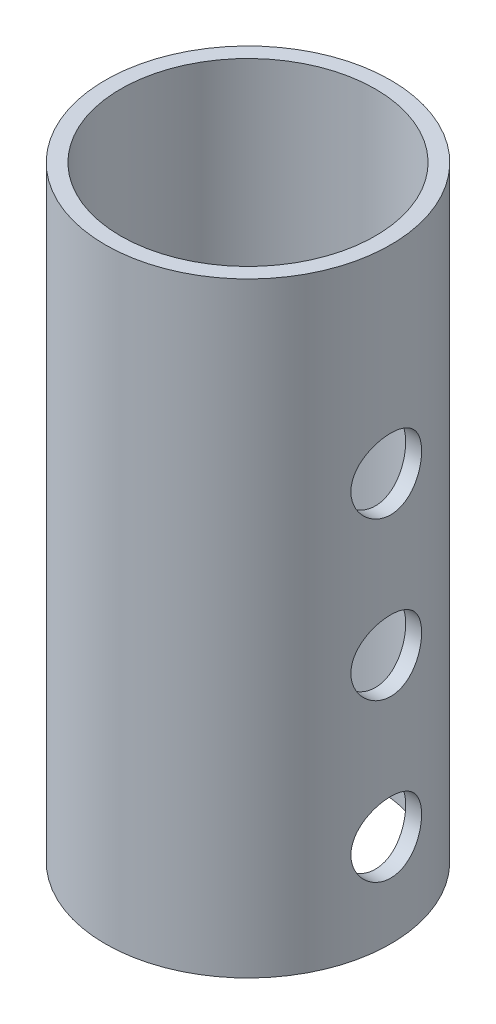
SolidWorks part; units mm, degrees
material "PTFE (general)"
ref_plane "Front Plane" through (0, 0, 0) normal (0, 0, 1) x (1, 0, 0)
ref_plane "Top Plane" through (0, 0, 0) normal (0, 1, 0) x (1, 0, 0)
ref_plane "Right Plane" through (0, 0, 0) normal (1, 0, 0) x (0, 0, -1)
sketch "Sketch1" plane through (0, 0, 0) normal (0, 1, 0) x (1, 0, 0)
  circle A0 centre (0, 0) radius 46.53
  circle A1 centre (0, 0) radius 41.53
  dimension "D1" = 5
  dimension "D2" = 83.06
extrude "Boss-Extrude1" add sketch "Sketch1" along normal blind 197.41
sketch "Sketch2" plane through (0, 0, 0) normal (1, 0, 0) x (0, 0, -1)
  line L0 (41.53, 197.41) -> (-41.53, 197.41) construction
  circle A0 centre (0, 132.71) radius 11.53
  circle A1 centre (0, 81.41) radius 11.53
  circle A2 centre (0, 30.11) radius 11.53
  dimension "D2" = 23.06
  dimension "D3" = 23.06
  dimension "D4" = 23.06
  dimension "D1" = 64.7
  dimension "D5" = 51.3
  dimension "D6" = 51.3
extrude "Cut-Extrude1" cut sketch "Sketch2" along normal through all
sketch "Sketch4" plane through (0, 0, 0) normal (1, 0, 0) x (0, 0, -1)
  circle A0 centre (0, 106.91) radius 7.5
  circle A4 centre (0, 81.41) radius 11.53 construction
  dimension "D1" = 15
  dimension "D3" = 25.5
extrude "Cut-Extrude2" cut sketch "Sketch4" against normal through all
